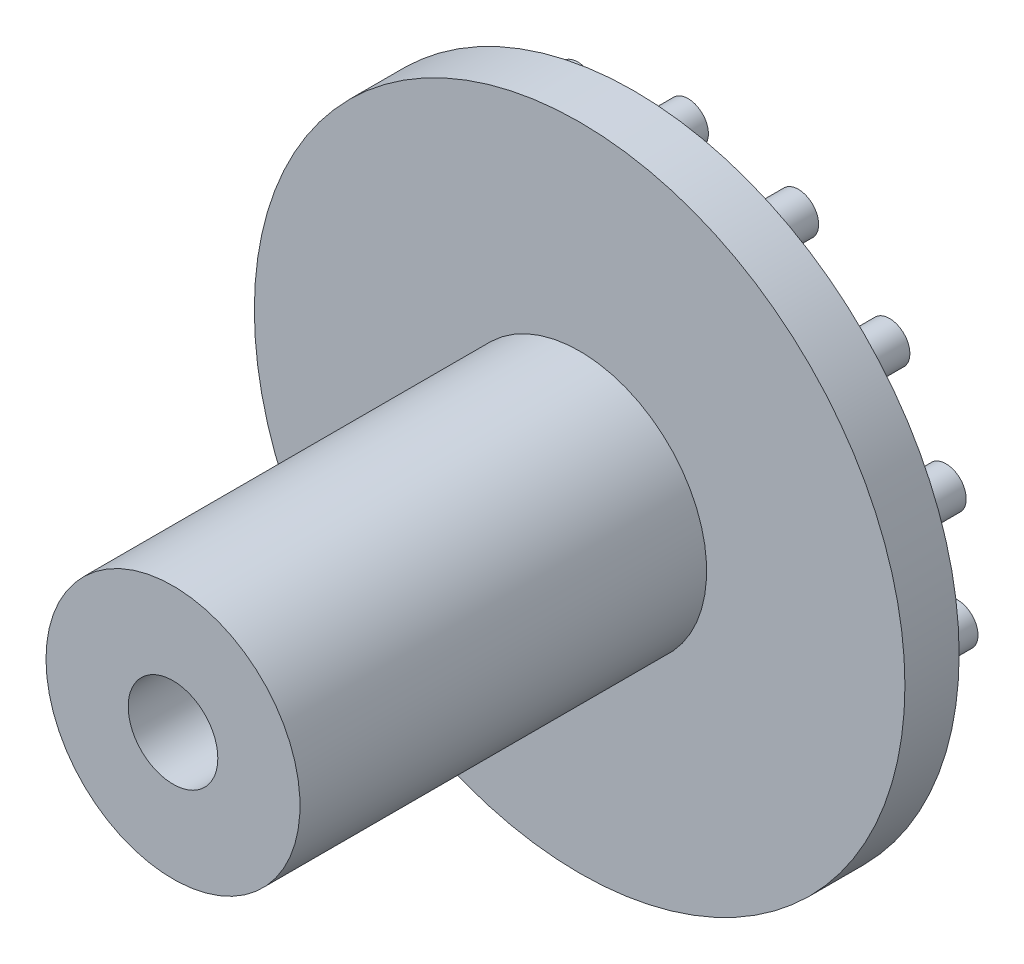
SolidWorks part; units mm, degrees
material "ABS"
ref_plane "Front Plane" through (0, 0, 0) normal (0, 0, 1) x (1, 0, 0)
ref_plane "Top Plane" through (0, 0, 0) normal (0, 1, 0) x (1, 0, 0)
ref_plane "Right Plane" through (0, 0, 0) normal (1, 0, 0) x (0, 0, -1)
sketch "Sketch1" plane through (0, 0, 0) normal (0, 0, 1) x (1, 0, 0)
  circle A0 centre (0, 0) radius 4.55
  circle A1 centre (0, 0) radius 15.24
  dimension "D1" = 9.1
  dimension "D2" = 30.48
extrude "Boss-Extrude1" add sketch "Sketch1" along normal blind 2.54
sketch "Sketch2" plane through (0, 0, 2.54) normal (0, 0, 1) x (1, 0, 0)
  circle A0 centre (0, 0) radius 5.95
  dimension "D1" = 11.9
extrude "Boss-Extrude2" add sketch "Sketch2" along normal blind 19.05
sketch "Sketch3" plane through (0, 0, 21.59) normal (0, 0, 1) x (1, 0, 0)
  line L1 (3.6662, 6.35) -> (-3.6662, 6.35)
  line L2 (-3.6662, 6.35) -> (-7.3323, 0)
  line L3 (-7.3323, 0) -> (-3.6662, -6.35)
  line L4 (-3.6662, -6.35) -> (3.6662, -6.35)
  line L5 (3.6662, -6.35) -> (7.3323, 0)
  line L6 (7.3323, 0) -> (3.6662, 6.35)
  circle A1 centre (0, 0) radius 6.35 construction
  dimension "D1" = 12.7
extrude "Boss-Extrude3" [suppressed] add sketch "Sketch3" along normal blind 38.1
sketch "Sketch4" [suppressed] plane through (0, 0, 47.64) normal (0, 0, 1) x (1, 0, 0)
  line L1 (-0.635, 1.905) -> (0.635, 1.905)
  line L2 (-0.635, 1.905) -> (-0.635, 4.445)
  line L3 (-0.635, 4.445) -> (0.635, 4.445)
  line L4 (0.635, 1.905) -> (0.635, 4.445)
  point P4 (0, 1.905)
  dimension "D1" = 2.54
  dimension "D2" = 1.905
  dimension "D3" = 1.27
extrude "Boss-Extrude4" [suppressed] add sketch "Sketch4" against normal blind 2.54
sketch "Sketch5" plane through (0, 0, 0) normal (0, 0, -1) x (-1, 0, 0)
  line L0 (0, 0) -> (0, 12.7) construction
  circle A0 centre (0, 12.7) radius 0.9525
  circle A13 centre (5.1656, 11.602) radius 0.9525
  circle A14 centre (9.4379, 8.498) radius 0.9525
  circle A15 centre (12.0784, 3.9245) radius 0.9525
  circle A16 centre (12.6304, -1.3275) radius 0.9525
  circle A17 centre (10.9985, -6.35) radius 0.9525
  circle A18 centre (7.4649, -10.2745) radius 0.9525
  circle A19 centre (2.6405, -12.4225) radius 0.9525
  circle A20 centre (-2.6405, -12.4225) radius 0.9525
  circle A21 centre (-7.4649, -10.2745) radius 0.9525
  circle A22 centre (-10.9985, -6.35) radius 0.9525
  circle A23 centre (-12.6304, -1.3275) radius 0.9525
  circle A24 centre (-12.0784, 3.9245) radius 0.9525
  circle A25 centre (-9.4379, 8.498) radius 0.9525
  circle A26 centre (-5.1656, 11.602) radius 0.9525
  dimension "D2" = 1.905
  dimension "D1" = 12.7
  dimension "D3" = 15
  dimension "D4" = 12.7
extrude "Boss-Extrude5" add sketch "Sketch5" along normal blind 2.54
sketch "Sketch6" plane through (0, 0, 21.59) normal (0, 0, 1) x (1, 0, 0)
  circle A1 centre (0, 0) radius 5.95
  circle A2 centre (0, 0) radius 5.95
  point P1 (0, 0)
  dimension "D1" = 0
hole_wizard "M5x0.8 Tapped Hole2" positions "Sketch6" profile "Sketch7" tap size "M5x0.8" standard "ANSI Metric" end condition through all
cosmetic thread "Hole Thread1" parameters "D2"=5
sketch "Sketch7" plane through (0, 0, 21.59) normal (1, 0, 0) x (0, -1, 0)
  line L0 (0, 0) -> (0, 24.13)
  line L1 (0, 24.13) -> (2.1, 24.13)
  line L2 (2.1, 24.13) -> (2.1, 0)
  line L5 (2.1, 0) -> (0, 0)
  line L11 (0, -6.35) -> (0, 107.95) construction
  dimension "Thru Tap Drill Dia." = 4.2
  dimension "Thru Tap Drill Depth" = 24.13
